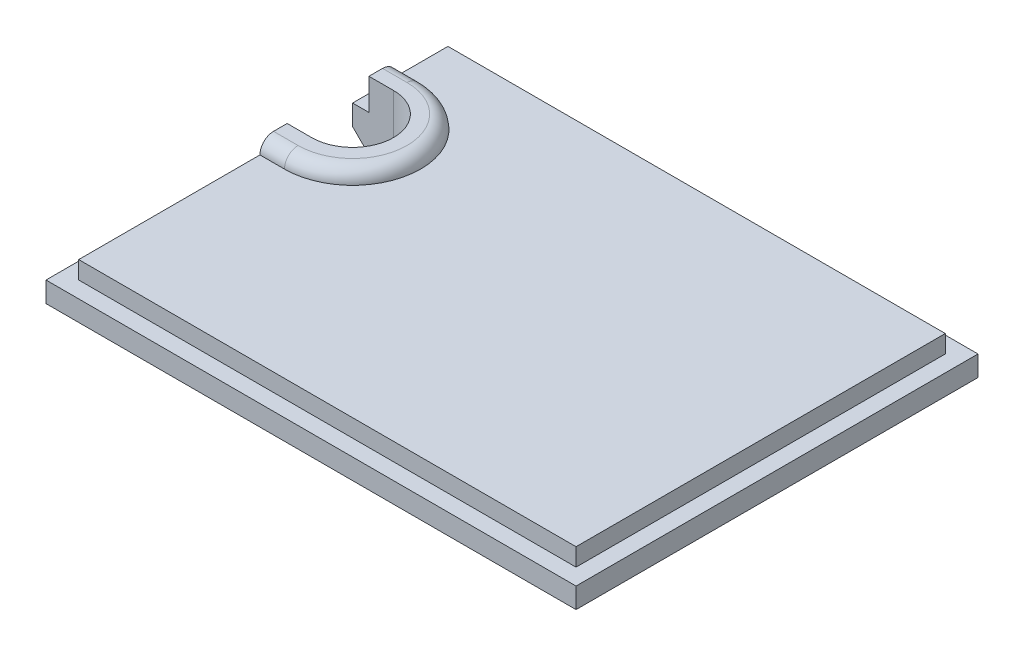
SolidWorks part; units mm, degrees
ref_plane "Front Plane" through (0, 0, 0) normal (0, 0, 1) x (1, 0, 0)
ref_plane "Top Plane" through (0, 0, 0) normal (0, 1, 0) x (1, 0, 0)
ref_plane "Right Plane" through (0, 0, 0) normal (1, 0, 0) x (0, 0, -1)
sketch "Sketch1" plane through (0, 0, 0) normal (0, 1, 0) x (1, 0, 0)
  line L0 (-19.45, 14.75) -> (-19.45, 7.75)
  line L1 (-19.45, -14.75) -> (19.45, -14.75)
  line L2 (19.45, -14.75) -> (19.45, 14.75)
  line L3 (19.45, 14.75) -> (-19.45, 14.75)
  line L4 (18.25, 13.55) -> (-18.25, 13.55)
  line L5 (-18.25, 13.55) -> (-18.25, 7.75)
  line L6 (-18.25, -13.55) -> (18.25, -13.55)
  line L7 (18.25, -13.55) -> (18.25, 13.55)
  line L8 (-18.25, 13.55) -> (0, 0) construction
  line L9 (0, 0) -> (18.25, -13.55) construction
  line L10 (0, 0) -> (18.25, 13.55) construction
  line L11 (0, 0) -> (-18.25, -13.55) construction
  line L12 (-16.45, 9.75) -> (-18.25, 9.75)
  line L13 (-18.25, 9.75) -> (-19.45, 9.75)
  line L14 (-16.45, 7.75) -> (-18.25, 7.75)
  line L15 (-18.25, 7.75) -> (-19.45, 7.75)
  line L16 (-16.45, 1.75) -> (-18.25, 1.75)
  line L17 (-18.25, 1.75) -> (-19.45, 1.75)
  line L18 (-16.45, -0.25) -> (-18.25, -0.25)
  line L19 (-18.25, -0.25) -> (-19.45, -0.25)
  line L20 (-19.45, 1.75) -> (-19.45, -14.75)
  line L21 (-19.45, 14.75) -> (-19.45, -14.75) construction
  line L22 (-18.25, 1.75) -> (-18.25, -13.55)
  line L23 (-18.25, 13.55) -> (-18.25, -13.55) construction
  arc A0 (-16.45, 7.75) -> (-16.45, 1.75) centre (-16.45, 4.75) cw
  arc A1 (-16.45, 9.75) -> (-16.45, -0.25) centre (-16.45, 4.75) cw
  arc A2 (-18.0956, 7.2584) -> (-16.45, 1.75) centre (-16.45, 4.75) cw construction
  arc A3 (-19.1926, 8.9307) -> (-16.45, -0.25) centre (-16.45, 4.75) cw construction
  dimension "D4" = 3
  dimension "D6" = 2
  dimension "D1" = 29.5
  dimension "D2" = 38.9
  dimension "D5" = 10
  dimension "D7" = 3
  dimension "D3" = 1.2
extrude "Boss-Extrude1" add sketch "Sketch1" along normal blind 1 contours L12 A1 L18 L5 L6 L7 L4 | A1 L12 L5 L14 A0 L16 L18 | L19 L5 L17 L0 | L15 L5 L13 L0 | L5 L19 L0 L1 L2 L3 L13 L4 L7 L6 | L17 L20 L1 L2 L3 L0 L15 L14 A0 L16 | L4 L5 L6 L7 region at (0, 0, -14.2618) region at (-18.85, 0, -8.75) region at (-17.35, 0, -9.6291) region at (0.9389, 0, 0.2919) region at (-18.85, 0, -0.75)
extrude "Boss-Extrude2" add sketch "Sketch1<5>" along normal blind 1.6 from surface contours L5 A1 L6 L7 L4 | A1 L5 A0 | A1 L0 A0 L5 | L0 A1 L5 L4 L7 L6 L1 L2 L3 | A1 L5 A0 L0 | L5 L0 | L5 L0 | L22 L17 L20 L19 region at (0, 0, -14.2618) region at (-18.85, 0, -8.75) region at (-17.35, 0, -9.6291) region at (0.9389, 0, 0.2919) region at (-18.85, 0, -0.75) starting at face at (-8.6, 1, -2.375)
sketch "Sketch1<5>" plane through (0, 0, 0) normal (0, 1, 0) x (1, 0, 0) same geometry as "Sketch1"
extrude "Boss-Extrude3" add sketch "Sketch1<6>" along normal blind 1.3 from surface contours L5 A1 L6 L7 L4 | A1 L5 A0 region at (-17.35, 0, -9.6291) region at (0.9389, 0, 0.2919) starting at face at (-8.6, 2.6, -2.375)
sketch "Sketch1<6>" plane through (0, 0, 0) normal (0, 1, 0) x (1, 0, 0) same geometry as "Sketch1"
extrude "Boss-Extrude4" add sketch "Sketch1<8>" along normal blind 1 from surface contours A1 L5 A0 region at (-17.35, 0, -9.6291) starting at face at (-8.3, 3.9, -2.375)
sketch "Sketch1<8>" plane through (0, 0, 0) normal (0, 1, 0) x (1, 0, 0) same geometry as "Sketch1"
fillet "Fillet1" radius 1 3 edges at (-11.45, 4.9, -4.75) (-17.35, 4.9, 0.25) (-17.35, 4.9, -9.75)
chamfer "Chamfer1" distance 1.1 angle 45 4 edges at (0, 0, -14.75) (19.45, 0, 0) (0, 0, 14.75) (-19.45, 0, -11.25)
